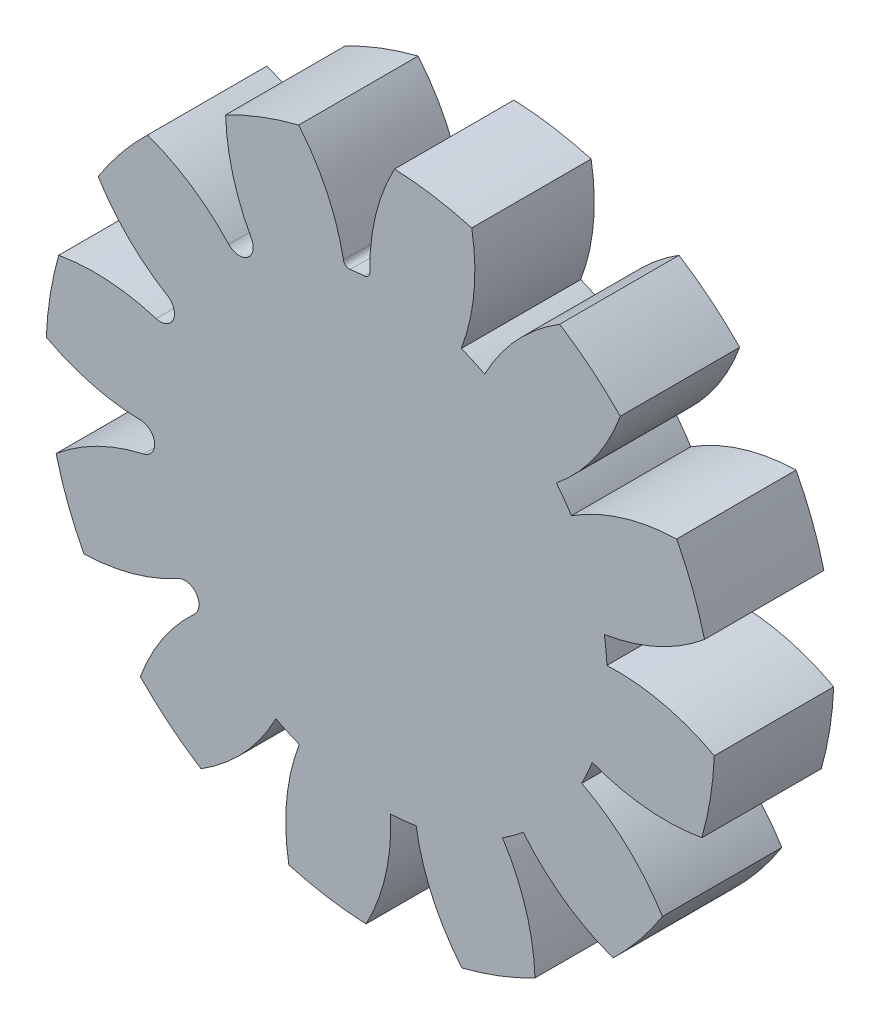
SolidWorks part; units mm, degrees
ref_plane "Front Plane" through (0, 0, 0) normal (0, 0, 1) x (1, 0, 0)
ref_plane "Top Plane" through (0, 0, 0) normal (0, 1, 0) x (1, 0, 0)
ref_plane "Right Plane" through (0, 0, 0) normal (1, 0, 0) x (0, 0, -1)
sketch "Sketch1" plane through (0, 0, 0) normal (0, 0, 1) x (1, 0, 0)
  circle A0 centre (0, 0) radius 12 construction
  circle A1 centre (0, 0) radius 14
  dimension "D1" = 24
  dimension "D2" = 28
extrude "Boss-Extrude1" add sketch "Sketch1" along normal mid plane 5 contours A1
sketch "Sketch2" plane through (0, 0, 2.5) normal (0, 0, 1) x (1, 0, 0)
  line L0 (0, 0) -> (1.0149, 13.9632) construction
  line L1 (0, 0) -> (3.4242, 13.5748) construction
  line L2 (0, 0) -> (-1.4252, 13.9273) construction
  line L3 (-1.5007, 9.3807) -> (0, 0) construction
  line L4 (-2.2574, 11.7858) -> (-0.1765, 11.9987) construction
  line L5 (-0.1765, 11.9987) -> (1.9097, 11.8471) construction
  line L6 (-3.1554, 13.6398) -> (-0.9244, 9.0337) construction
  circle A0 centre (0, 0) radius 10
  arc A1 (-0.4304, 9.4902) -> (-1.5007, 9.3807) centre (0, 0) ccw
  circle A2 centre (0, 0) radius 14 construction
  arc A3 (-3.417, 13.5766) -> (-1.5007, 9.3807) centre (-10.0451, 8.0138) cw
  arc A4 (0.5963, 13.9873) -> (-0.4304, 9.4902) centre (8.2138, 9.8823) ccw
  circle A5 centre (0, 0) radius 12 construction
  point P21 (0, 0)
  point P22 (-0.3536, 6.3209)
  dimension "D4" = 24
  dimension "D1" = 20
  dimension "D2" = 4
  dimension "D3" = 4.5
  dimension "D5" = 20
extrude "Cut-Extrude1" cut sketch "Sketch2" against normal blind 5 and the other way through all contours A4 A1 A3
fillet "Fillet1" radius 0.25 2 edges at (-0.4304, 9.4902, 0) (-1.5007, 9.3807, 0)
pattern_circular "CirPattern1" count 12 over 360 about axis through (0, 0, 2.5) along (0, 0, 1) of "Cut-Extrude1"
fillet "Fillet2" radius 0.6 2 edges at (-5.99, 7.3736, 0) (-5.1179, 8.0036, 0)
fillet "Fillet3" radius 0.6 2 edges at (-8.8743, 3.3908, 0) (-8.434, 4.3724, 0)
fillet "Fillet4" radius 0.6 2 edges at (-9.3807, -1.5007, 0) (-9.4902, -0.4304, 0)
fillet "Fillet5" radius 0.6 2 edges at (-7.3736, -5.99, 0) (-8.0036, -5.1179, 0)
equation "\"Module\"= 2"
equation "\"Number of teeth\"= 12"
equation "\"Pressure Angle\"= 20deg"
equation "\"D1@Sketch1\"=\"Module\" * \"Number of teeth\""
equation "\"D2@Sketch1\"=(\"Number of teeth\" +2) *\"Module\""
equation "\"D2@Sketch2\"=\"Module\" *2"
equation "\"D3@Sketch2\"=\"Module\"*if( \"Module\"=>1.25,2.25,2.4)"
equation "\"D4@Sketch2\"=\"Module\"*\"Number of teeth\""
equation "\"D5@Sketch2\"=\"Pressure Angle\""
equation "\"D1@Fillet2\"=\"Module\"*0.3"
equation "\"D1@Fillet3\"=\"Module\" * 0.3"
equation "\"D1@Fillet4\"=\"Module\" *0.3"
equation "\"D1@Fillet5\"=\"Module\" *0.3"
equation "\"D1@CirPattern1\"=\"Number of teeth\""
